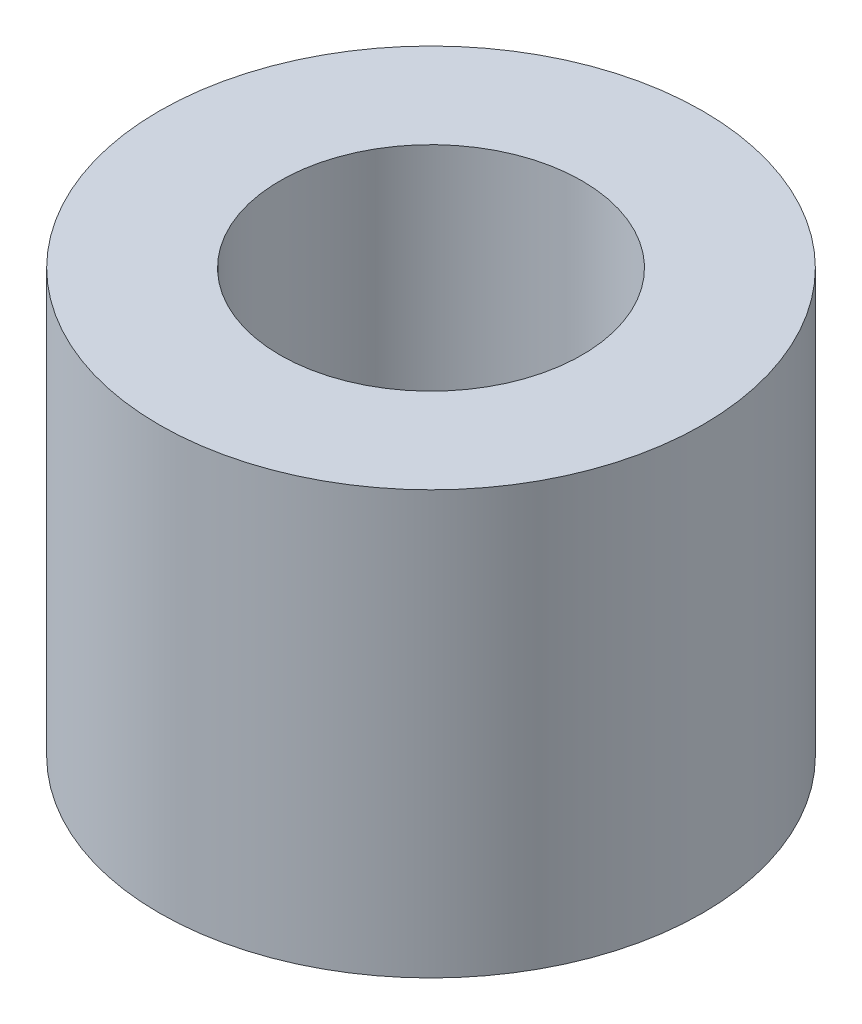
SolidWorks part; units mm, degrees
ref_plane "Front Plane" through (0, 0, 0) normal (0, 0, 1) x (1, 0, 0)
ref_plane "Top Plane" through (0, 0, 0) normal (0, 1, 0) x (1, 0, 0)
ref_plane "Right Plane" through (0, 0, 0) normal (1, 0, 0) x (0, 0, -1)
sketch "Sketch1" plane through (0, 0, 0) normal (0, 1, 0) x (1, 0, 0)
  circle A0 centre (0, 0) radius 3.175
  circle A1 centre (0, 0) radius 5.715
  dimension "D1" = 6.35
  dimension "D2" = 2.54
extrude "Boss-Extrude1" add sketch "Sketch1" along normal blind 8.89
